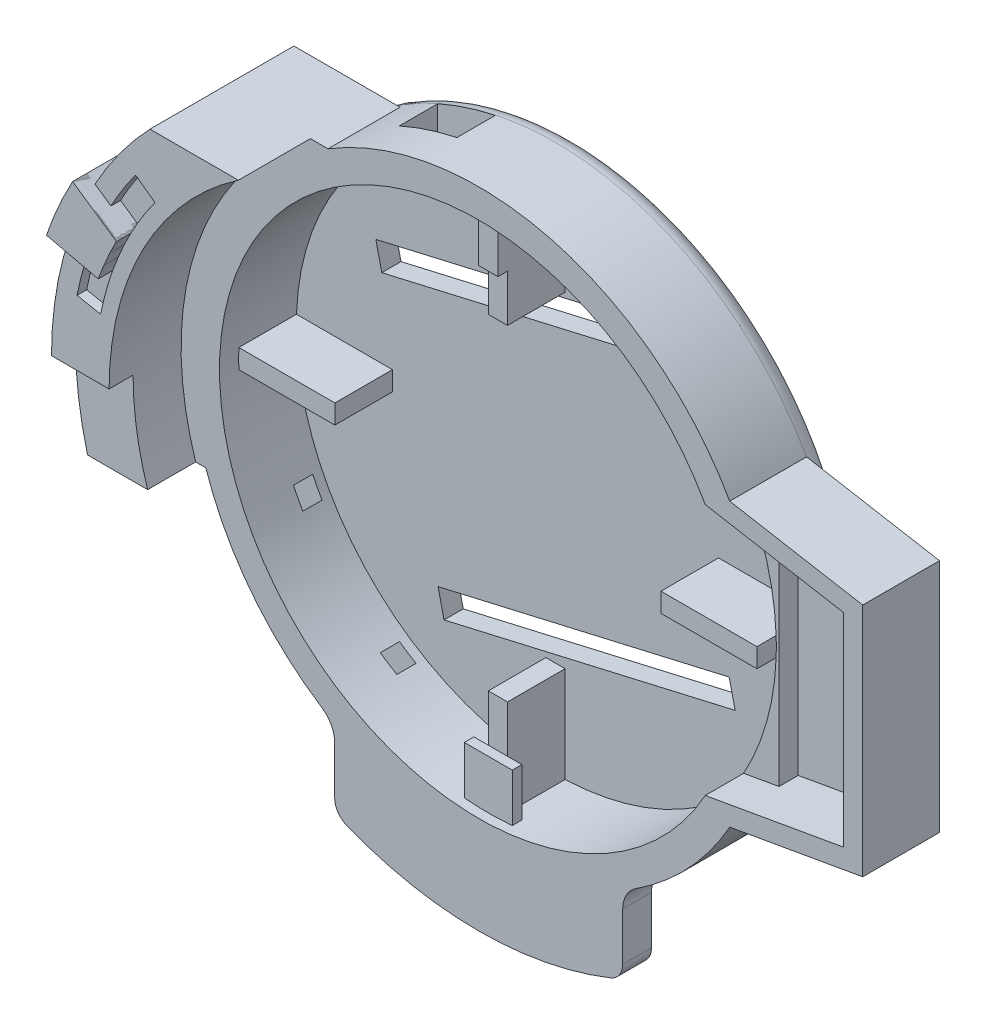
SolidWorks part; units mm, degrees
material "AISI 304"
ref_plane "Front Plane" through (0, 0, 0) normal (0, 0, 1) x (1, 0, 0)
ref_plane "Top Plane" through (0, 0, 0) normal (0, 1, 0) x (1, 0, 0)
ref_plane "Right Plane" through (0, 0, 0) normal (1, 0, 0) x (0, 0, -1)
sketch "草图1" plane through (0, 0, 0) normal (0, 0, 1) x (1, 0, 0)
  circle A0 centre (0, 0) radius 30
  dimension "D1" = 60
extrude "凸台-拉伸1" add sketch "草图1" along normal blind 2
sketch "草图5" plane through (0, 0, 2) normal (0, 0, 1) x (1, 0, 0)
  circle A0 centre (0, 0) radius 30
  circle A1 centre (0, 0) radius 27
  dimension "D1" = 60
  dimension "D2" = 54
extrude "凸台-拉伸2" add sketch "草图5" along normal blind 10 contours A0 | A1
sketch "草图6" plane through (0, 0, 12) normal (0, 0, 1) x (1, 0, 0)
  line L0 (-15, -25.9808) -> (-15, -33.9808)
  line L2 (15, -33.9808) -> (15, -25.9808)
  circle A0 centre (0, 0) radius 30 construction
  arc A1 (-15, -25.9808) -> (15, -25.9808) centre (0, 0) ccw
  arc A2 (-15, -33.9808) -> (15, -33.9808) centre (0, 0) ccw
  dimension "D2" = 30
  dimension "D1" = 8
extrude "凸台-拉伸3" add sketch "草图6" against normal blind 3
fillet "圆角2" radius 3 1 edges at (-15, -25.9808, 10.5)
fillet "圆角3" radius 3 1 edges at (15, -25.9808, 10.5)
sketch "草图8" plane through (0, 0, 12) normal (0, 0, 1) x (1, 0, 0)
  line L0 (26.0356, -14.9047) -> (40, -14.9047)
  line L1 (40, -14.9047) -> (40, 14.9047)
  line L2 (40, 14.9047) -> (26.0356, 14.9047)
  circle A0 centre (0, 0) radius 30 construction
  arc A1 (26.0356, -14.9047) -> (26.0356, 14.9047) centre (0, 0) ccw
  point P4 (30, 0)
  dimension "D1" = 10
extrude "凸台-拉伸4" add sketch "草图8" against normal blind 6
sketch "草图13" plane through (0, 0, 12) normal (0, 0, 1) x (1, 0, 0)
  line L0 (-26.7466, 25.566) -> (-15.6965, 25.566)
  line L1 (-37, 0) -> (-30, 0)
  arc A0 (-26.7466, 25.566) -> (-37, 0) centre (0, 0) ccw
  arc A1 (-15.6965, 25.566) -> (-30, 0) centre (0, 0) ccw
  dimension "D1" = 37
  dimension "D2" = 30
extrude "凸台-拉伸6" add sketch "草图13" against normal mid plane 15
sketch "草图14" plane through (0, 0, 19.5) normal (0, 0, 1) x (1, 0, 0)
  circle A0 centre (0, 0) radius 31
  dimension "D1" = 62
extrude "切除-拉伸3" cut sketch "草图14" against normal up to surface (7.5 mm away) up to face at (6.8931, -11.869, 12)
chamfer "倒角4" distance 15 angle 10 1 edges at (40, 14.9047, 9) first distance on face at (33.0178, 14.9047, 9)
chamfer "倒角5" distance 15 angle 10 1 edges at (40, -14.9047, 9) first distance on face at (33.0178, -14.9047, 9)
sketch "草图16" plane through (0, 0, 12) normal (0, 0, 1) x (1, 0, 0)
  line L0 (28.2902, 12.2937) -> (38, 10.5816)
  line L1 (38, 10.5816) -> (38, -10.5816)
  line L2 (38, -10.5816) -> (22.2888, -13.3519)
  line L3 (22.2888, -13.3519) -> (18.7468, 13.9764)
  line L4 (18.7468, 13.9764) -> (28.2902, 12.2937)
  line L5 (26.1507, -14.7018) -> (40, -12.2598) construction
  line L6 (40, -12.2598) -> (40, 12.2598) construction
  line L7 (40, 12.2598) -> (26.1507, 14.7018) construction
  line L8 (26.1507, -14.7018) -> (40, -12.2598)
  line L9 (40, -12.2598) -> (40, 12.2598)
  line L10 (40, 12.2598) -> (26.1507, 14.7018)
  circle M23 centre (0, 0) radius 27
  dimension "D1" = 2
  dimension "D2" = 2
  dimension "D3" = 2
extrude "切除-拉伸6" cut sketch "草图16" against normal blind 4 contours L4 L3 L2 M23 | L4 L2 L1 L0 M23 region at (31.7381, 0, 12) region at (23.1904, 1.5488, 12)
sketch "草图17" plane through (0, 0, 12) normal (0, 0, 1) x (1, 0, 0)
  line L0 (-28.4305, -9.5763) -> (-35.7393, -9.5763)
  line L1 (-37, 0) -> (-31, 0) construction
  line L2 (-30, 0) -> (-31, 0) construction
  line L3 (-37, 0) -> (-31, 0)
  line L4 (-30, 0) -> (-31, 0)
  arc A0 (-37, 0) -> (-35.7393, -9.5763) centre (0, 0) ccw
  arc A1 (-30, 0) -> (-28.4305, -9.5763) centre (0, 0) ccw
extrude "凸台-拉伸10" add sketch "草图17" along normal mid plane 10
sketch "草图18" plane through (0, 0, 12) normal (0, 0, 1) x (1, 0, 0)
  line L0 (-35.7393, -9.5763) -> (-28.4305, -9.5763) construction
  line L1 (-30, 0) -> (-31, 0) construction
  line L2 (-35.7393, -9.5763) -> (-28.4305, -9.5763)
  line L3 (-30, 0) -> (-31, 0)
  circle A0 centre (0, 0) radius 31
  circle A1 centre (0, 0) radius 30 construction
  circle A2 centre (0, 0) radius 30
  line M9 (-31, 0) -> (-30, 0)
  arc M10 (-30, 0) -> (-28.4305, -9.5763) centre (0, 0) ccw
extrude "切除-拉伸7" cut sketch "草图18" along normal blind 6 contours A0 L2 M9 M10 region at (-29.984, -4.8293, 12)
sketch "草图19" plane through (0, 0, 2) normal (0, 0, 1) x (1, 0, 0)
  line L0 (-1, 26.9815) -> (-1, 16.9815)
  line L1 (-1, 16.9815) -> (1, 16.9815)
  line L2 (1, 16.9815) -> (1, 26.9815)
  line L3 (26.9815, 1) -> (16.9815, 1)
  line L4 (16.9815, -1) -> (26.9815, -1)
  line L5 (16.9815, 1) -> (16.9815, -1)
  line L6 (1, -26.9815) -> (1, -16.9815)
  line L7 (-1, -16.9815) -> (-1, -26.9815)
  line L8 (1, -16.9815) -> (-1, -16.9815)
  line L9 (-26.9815, -1) -> (-16.9815, -1)
  line L10 (-16.9815, 1) -> (-26.9815, 1)
  line L11 (-16.9815, -1) -> (-16.9815, 1)
  circle A0 centre (0, 0) radius 27 construction
  arc A1 (23.5974, 13.1211) -> (23.5974, -13.1211) centre (0, 0) ccw construction
  arc A2 (1, 26.9815) -> (-1, 26.9815) centre (0, 0) ccw
  arc A3 (26.9815, -1) -> (26.9815, 1) centre (0, 0) ccw
  arc A4 (-1, -26.9815) -> (1, -26.9815) centre (0, 0) ccw
  arc A5 (-26.9815, 1) -> (-26.9815, -1) centre (0, 0) ccw
  point P26 (0, 0)
  dimension "D1" = 4
extrude "凸台-拉伸11" add sketch "草图19" along normal blind 8
sketch "草图20" plane through (0, 0, 10) normal (0, 0, 1) x (1, 0, 0)
  line L0 (-1, 26.9815) -> (-1, 21.884)
  line L1 (-1, 21.884) -> (1, 21.884)
  line L2 (1, 21.884) -> (1, 26.9815)
  line L9 (-1, 26.9815) -> (-1, 16.9815)
  line L10 (-1, 16.9815) -> (1, 16.9815)
  line L11 (1, 16.9815) -> (1, 26.9815)
  line L12 (-1, 26.9815) -> (-1, 21.884)
  line L14 (1, 21.884) -> (1, 26.9815)
  line L17 (2.5, -21.884) -> (2.5, -26.884)
  line L18 (-2.5, -26.884) -> (-2.5, -21.884)
  line L19 (2.5, -21.884) -> (2.5, -26.884)
  line L20 (-2.5, -21.884) -> (2.5, -21.884)
  line L21 (-2.5, -26.884) -> (-2.5, -21.884)
  arc A0 (2.5, -26.884) -> (-2.5, -26.884) centre (0, 0) cw
  arc A3 (1, 26.9815) -> (-1, 26.9815) centre (0, 0) ccw
  arc A4 (1, 26.9815) -> (-1, 26.9815) centre (0, 0) ccw
  arc M11 (1, 26.9815) -> (-1, 26.9815) centre (0, 0) ccw
  line M12 (-1, 26.9815) -> (-1, 16.9815)
  line M14 (1, 16.9815) -> (1, 26.9815)
  dimension "D1" = 0
extrude "凸台-拉伸12" add sketch "草图20" along normal blind 1 contours A0 L17 L20 L18 | L1 M12 M14 M11 region at (0, 24.4389, 10) region at (0, -24.4228, 10)
sketch "草图21" plane through (0, 0, 19.5) normal (0, 0, 1) x (1, 0, 0)
  line L2 (-28.7344, 15.1849) -> (-33.2959, 18.3135)
  line L3 (-30.6288, 10.8687) -> (-36.0194, 12.1079)
  arc A0 (-33.2959, 18.3135) -> (-36.0194, 12.1079) centre (0, 0) ccw
  arc A1 (-28.7344, 15.1849) -> (-30.6288, 10.8687) centre (0, 0) ccw
extrude "凸台-拉伸13" add sketch "草图21" along normal blind 1.5
sketch "草图26" plane through (0, 0, 21) normal (0, 0, 1) x (1, 0, 0)
  line L2 (-28.7344, 15.1849) -> (-33.2959, 18.3135)
  line L3 (-36.0194, 12.1079) -> (-30.6288, 10.8687)
  line L4 (-28.7344, 15.1849) -> (-33.2959, 18.3135)
  line L5 (-36.0194, 12.1079) -> (-30.6288, 10.8687)
  arc A2 (-28.7344, 15.1849) -> (-30.6288, 10.8687) centre (0, 0) ccw
  arc A3 (-33.2959, 18.3135) -> (-36.0194, 12.1079) centre (0, 0) ccw
  arc A4 (-28.7344, 15.1849) -> (-30.6288, 10.8687) centre (0, 0) ccw
  arc A5 (-33.2959, 18.3135) -> (-36.0194, 12.1079) centre (0, 0) ccw
  dimension "D1" = 0
extrude "凸台-拉伸14" add sketch "草图26" against normal up to surface (16.5 mm away) separate body contours A4 L5 A5 L4 up to face at (-28.8109, 13.4966, 4.5)
sketch "草图28" plane through (0, 0, 19.5) normal (0, 0, 1) x (1, 0, 0)
  line L1 (-26.2215, 19.2011) -> (-28.2386, 20.6781)
  line L2 (-31.8835, 6.3003) -> (-34.3361, 6.7849)
  line L3 (-35.04, 11.8827) -> (-30.6288, 10.8687) construction
  line L4 (-35.04, 11.8827) -> (-30.6288, 10.8687)
  line L5 (-28.7344, 15.1849) -> (-32.4671, 17.7451) construction
  line L6 (-28.7344, 15.1849) -> (-32.4671, 17.7451)
  arc A0 (-30.6288, 10.8687) -> (-31.8835, 6.3003) centre (0, 0) ccw
  arc A1 (-33.0803, 11.4322) -> (-34.3361, 6.7849) centre (0, 0) ccw
  arc A3 (-26.2215, 19.2011) -> (-28.7344, 15.1849) centre (0, 0) ccw
  arc A4 (-28.2386, 20.6781) -> (-30.8088, 16.6077) centre (0, 0) ccw
  line M5 (-30.6288, 10.8687) -> (-35.04, 11.8827)
extrude "切除-拉伸8" cut sketch "草图28" against normal blind 1 contours A1 L2 A0 M5 | L1 A4 L6 A3 region at (-28.5514, 17.9499, 19.5) region at (-32.5399, 8.8621, 19.5)
sketch "草图31" plane through (0, 0, 6) normal (0, 0, -1) x (-1, 0, 0)
  line L3 (-40, 12.2598) -> (-40, -12.2598)
  line L4 (-40, -12.2598) -> (-26.1507, -14.7018)
  line L5 (-26.1507, 14.7018) -> (-40, 12.2598)
  line L6 (-40, 12.2598) -> (-40, -12.2598)
  line L7 (-40, -12.2598) -> (-26.1507, -14.7018)
  line L8 (-26.1507, 14.7018) -> (-40, 12.2598)
  arc A1 (-26.1507, 14.7018) -> (-26.1507, -14.7018) centre (0, 0) ccw
  arc A2 (-26.1507, 14.7018) -> (-26.1507, -14.7018) centre (0, 0) ccw
  dimension "D1" = 0
extrude "凸台-拉伸15" add sketch "草图31" along normal blind 2
sketch "草图32" plane through (0, 0, 8) normal (0, 0, 1) x (1, 0, 0)
  line L0 (38, -10.5816) -> (23.5974, -13.1211) construction
  line L1 (38, 10.5816) -> (38, -10.5816) construction
  line L2 (23.5974, 13.1211) -> (38, 10.5816) construction
  line L3 (38, -10.5816) -> (27.2851, -12.4709)
  line L4 (38, 10.5816) -> (38, -10.5816)
  line L5 (27.2851, 12.4709) -> (38, 10.5816)
  line L6 (27.2851, 12.4709) -> (27.2851, -12.4709)
  circle A0 centre (0, 0) radius 30 construction
extrude "切除-拉伸9" cut sketch "草图32" against normal blind 2
sketch "草图33" plane through (0, 0, 0) normal (0, 0, -1) x (-1, 0, 0)
  circle A0 centre (0, 0) radius 30
extrude "切除-拉伸10" cut sketch "草图33" against normal blind 2
sketch "草图34" plane through (0, 0, 2) normal (0, 0, -1) x (-1, 0, 0)
  circle A0 centre (0, 0) radius 30
extrude "凸台-拉伸16" add sketch "草图34" against normal blind 2
fillet "圆角4" radius 2 1 edges at (-15, -33.9808, 10.5)
fillet "圆角5" radius 2 1 edges at (15, -33.9808, 10.5)
sketch "草图35" plane through (0, 0, 4) normal (0, 0, 1) x (1, 0, 0)
  line L0 (0, 30) -> (0, -27) construction
  line L1 (-18.7138, 11.8869) -> (11.6089, 18.8874)
  line L2 (-18.7138, 11.8869) -> (-18.0923, 9.1949)
  line L3 (-18.0923, 9.1949) -> (12.2304, 16.1954)
  line L4 (11.6089, 18.8874) -> (12.2304, 16.1954)
  line L5 (-16.884, 0) -> (16.884, 0) construction
  line L6 (0, 0) -> (54.0246, 12.4726) construction
  line L7 (-12.2304, -16.1954) -> (18.0923, -9.1949)
  line L12 (18.7138, -11.8869) -> (18.0923, -9.1949)
  line L13 (-11.6089, -18.8874) -> (18.7138, -11.8869)
  line L14 (-11.6089, -18.8874) -> (-12.2304, -16.1954)
  dimension "D1" = 13
extrude "切除-拉伸11" cut sketch "草图35" against normal blind 10
fillet "圆角6" radius 2 1 edges at (-30, 0, 2)
ref_plane "基准面1" through (7.9907, 7.9907, 0) normal (-0.7071, -0.7071, 0) x (0, 0, 1)
sketch "草图37" plane through (7.9907, 7.9907, 0) normal (-0.7071, -0.7071, 0) x (0, 0, 1)
  line L1 (4.9344, 8.986) -> (6.9344, 8.986)
  line L2 (4.9344, 8.986) -> (4.9344, 6.986)
  line L3 (4.9344, 6.986) -> (6.9344, 6.986)
  line L4 (6.9344, 8.986) -> (6.9344, 6.986)
  line L5 (4.9344, -4.8884) -> (6.9344, -4.8884)
  line L6 (4.9344, -4.8884) -> (4.9344, -6.8884)
  line L7 (4.9344, -6.8884) -> (6.9344, -6.8884)
  line L8 (6.9344, -4.8884) -> (6.9344, -6.8884)
extrude "切除-拉伸12" cut sketch "草图37" along normal blind 65 contours L2 L1 L4 L3 | L6 L5 L8 L7
ref_plane "基准面2" through (-21.9406, -20.46, 0) normal (-0.7314, -0.682, 0) x (0, 0, -1)
sketch "草图38" plane through (0, 0, 0) normal (0, 1, 0) x (1, 0, 0)
  line L7 (-12.2168, -8.0519) -> (-12.2168, -4.0519)
  line L8 (-6.2168, -4.0519) -> (-12.2168, -4.0519)
  line L9 (-6.2168, -8.0519) -> (-6.2168, -4.0519)
  line L10 (-6.2168, -8.0519) -> (-12.2168, -8.0519)
extrude "切除-拉伸14" cut sketch "草图38" along normal blind 45
ref_plane "基准面3" through (-7.9907, 7.9907, 0) normal (0.7071, -0.7071, 0) x (-0.7071, -0.7071, 0)
ref_plane "基准面4" through (-0.9197, 0.9197, 0) normal (0.7071, -0.7071, 0) x (-0.7071, -0.7071, 0)
